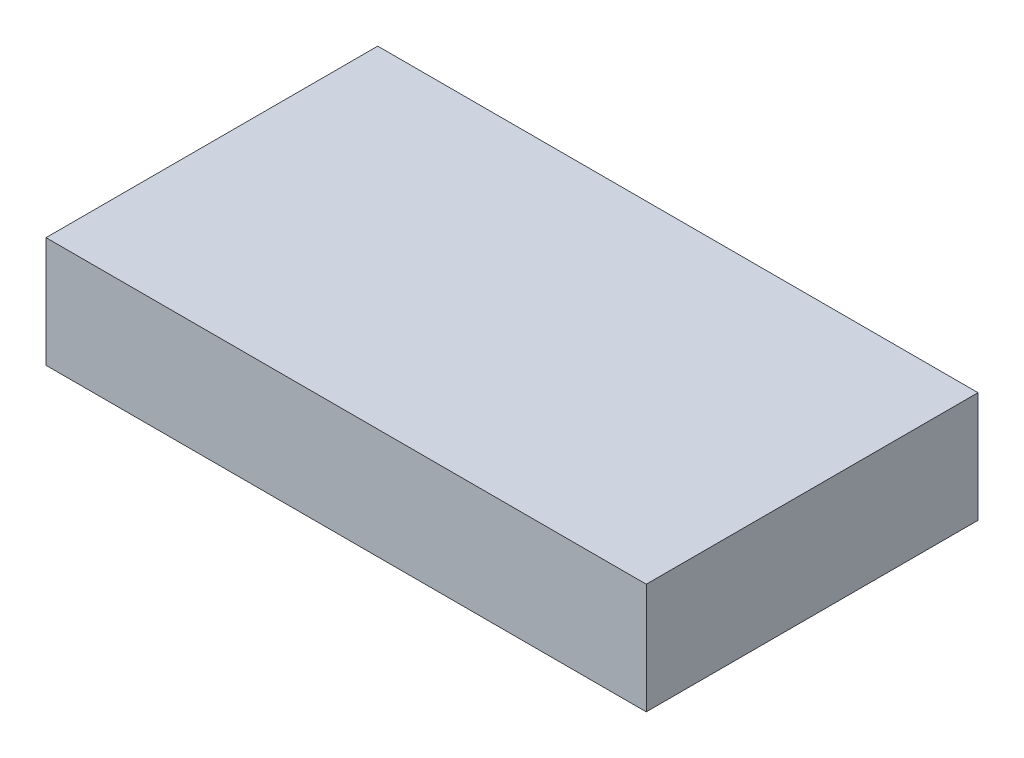
SolidWorks part; units mm, degrees
ref_plane "Front Plane" through (0, 0, 0) normal (0, 0, 1) x (1, 0, 0)
ref_plane "Top Plane" through (0, 0, 0) normal (0, 1, 0) x (1, 0, 0)
ref_plane "Right Plane" through (0, 0, 0) normal (1, 0, 0) x (0, 0, -1)
sketch "Sketch1" plane through (0, 0, 0) normal (0, 1, 0) x (1, 0, 0)
  line L0 (0, 0) -> (38, 0)
  line L1 (38, 0) -> (38, 21)
  line L2 (38, 21) -> (0, 21)
  line L3 (0, 21) -> (0, 0)
  dimension "D1" = 38
  dimension "D2" = 21
extrude "Boss-Extrude1" add sketch "Sketch1" along normal blind 7
